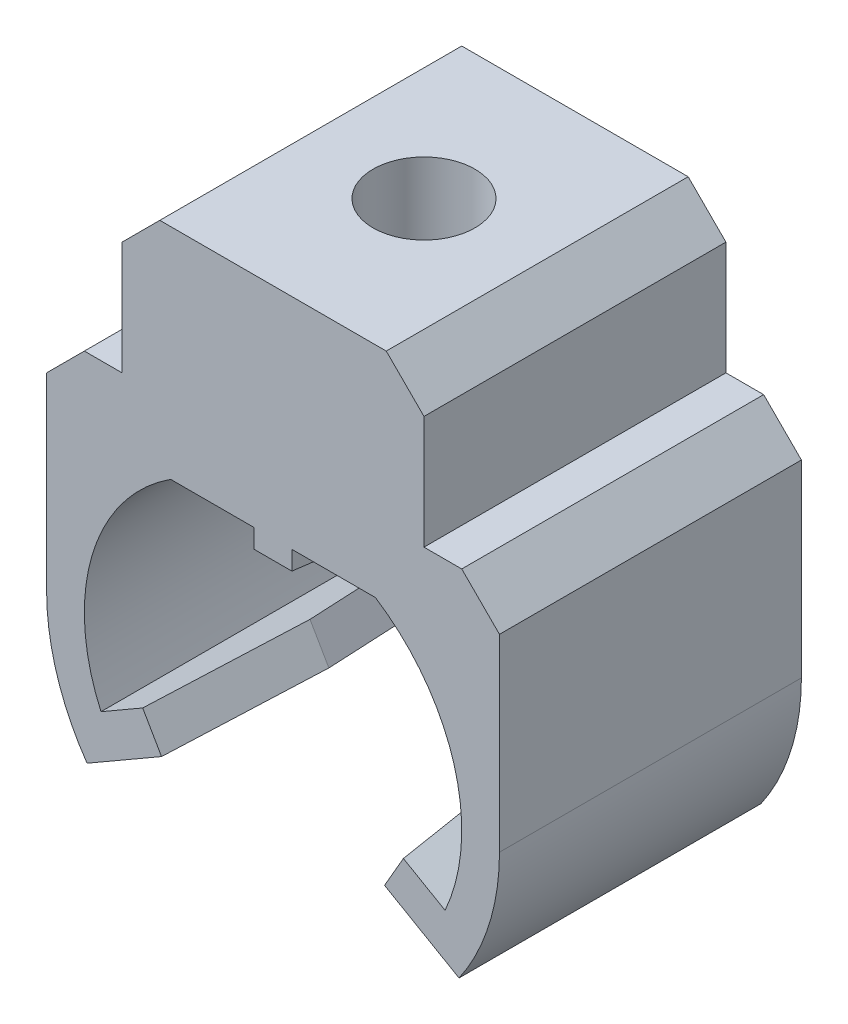
SolidWorks part; units mm, degrees
material "PTFE (general)"
ref_plane "Front Plane" through (0, 0, 0) normal (0, 0, 1) x (1, 0, 0)
ref_plane "Top Plane" through (0, 0, 0) normal (0, 1, 0) x (1, 0, 0)
ref_plane "Right Plane" through (0, 0, 0) normal (1, 0, 0) x (0, 0, -1)
sketch "Sketch1" plane through (0, 0, 0) normal (0, 0, 1) x (1, 0, 0)
  line L0 (-2.7129, 4.2) -> (-0.5, 4.2)
  line L1 (-3.0213, -1.167) -> (-2.5213, -2.033)
  line L2 (-6, 0) -> (-6, 6)
  line L3 (-6, 6) -> (-4, 6)
  line L4 (6, 0) -> (6, 6)
  line L5 (-0.5, 3.2) -> (0.5, 3.2)
  line L6 (2.5213, -2.033) -> (3.0213, -1.167)
  line L7 (-4, 6) -> (-4, 10)
  line L8 (-4, 10) -> (4, 10)
  line L9 (0, 0) -> (5.1962, -3) construction
  line L10 (4, 10) -> (4, 6)
  line L11 (3.0213, -1.167) -> (4.5584, -2.0545)
  line L12 (4, 6) -> (6, 6)
  line L13 (0.25, 0.433) -> (5.4462, -2.567) construction
  line L14 (0, 0) -> (-5.1962, -3) construction
  line L15 (-0.5, 3.2) -> (-0.5, 4.2)
  line L16 (0.5, 4.2) -> (2.7129, 4.2)
  line L17 (0.5, 3.2) -> (0.5, 4.2)
  line L23 (2.5213, -2.033) -> (4.9281, -3.4226)
  line L24 (-2.5213, -2.033) -> (-4.9281, -3.4226)
  line L25 (-3.0213, -1.167) -> (-4.5584, -2.0545)
  arc A0 (-6, 0) -> (-4.9281, -3.4226) centre (0, 0) ccw
  arc A1 (4.5584, -2.0545) -> (2.7129, 4.2) centre (0, 0) ccw
  arc A2 (4.9281, -3.4226) -> (6, 0) centre (0, 0) ccw
  arc A4 (-2.7129, 4.2) -> (-4.5584, -2.0545) centre (0, 0) ccw
  circle A5 centre (0, 0) radius 3.2 construction
  point P7 (-0.3536, -0.3536)
  point P13 (4.057, -4.7641)
  point P20 (-0.3536, -0.3536)
  point P22 (-0.3536, 0.3536)
  point P29 (-4.5962, -3.8891)
  point P30 (0.3536, -0.3536)
  point P31 (-3.8891, -4.5962)
  point P32 (-0.3536, -0.3536)
  point P33 (-4.5962, 3.8891)
  point P34 (0.3536, 0.3536)
  point P35 (-3.8891, 4.5962)
  point P36 (-0.3536, 0.3536)
  point P37 (3.8891, 4.5962)
  point P39 (4.5962, 3.8891)
  point P43 (-4, 7.1082)
  dimension "D1" = 6
  dimension "D5" = 10
  dimension "D6" = 6.4
  dimension "D2" = 6
  dimension "D3" = 4
  dimension "D4" = 30
  dimension "D8" = 8
  dimension "D9" = 0.5
  dimension "D10" = 0.5
  dimension "D11" = 30
  dimension "D12" = 0.5
  dimension "D13" = 4
  dimension "D14" = 0.5
  dimension "D15" = 0.5
  dimension "D16" = 1
  dimension "D17" = 6
  dimension "D7" = 0.5
extrude "Boss-Extrude2" add sketch "Sketch1" along normal blind 8
ref_axis "Axis1" through (0, 0, 8) along (0, 0, -1)
ref_plane "Plane1" through (0, 0, 0) normal (0, 1, 0) x (-1, 0, 0)
sketch "Sketch11" plane through (0, 10, 0) normal (0, 1, 0) x (1, 0, 0)
  line L0 (0, -8) -> (0, 0) construction
  line L1 (4, -8) -> (-4, -8) construction
  circle A0 centre (0, -4) radius 1.35
  dimension "D1" = 2.7
  dimension "D2" = 4
extrude "Cut-Extrude5" cut sketch "Sketch11" against normal blind 5
chamfer "Chamfer1" distance 1 angle 45 4 edges at (-6, 6, 4) (6, 6, 4) (-4, 10, 4) (4, 10, 4)
chamfer "Chamfer2" distance 4 distance2 0.5 4 edges at (2.7713, -1.6, 8) (2.7713, -1.6, 0) (0, 3.2, 8) (-2.7713, -1.6, 8) first distance on face at (2.7713, -1.6, 4) first distance on face at (0, 3.2, 4) first distance on face at (-2.7713, -1.6, 4)
chamfer "Chamfer3" distance 0.5 distance2 4 2 edges at (-2.7713, -1.6, 0) (0, 3.2, 0) first distance on face at (0.0333, 2.9949, 0)
